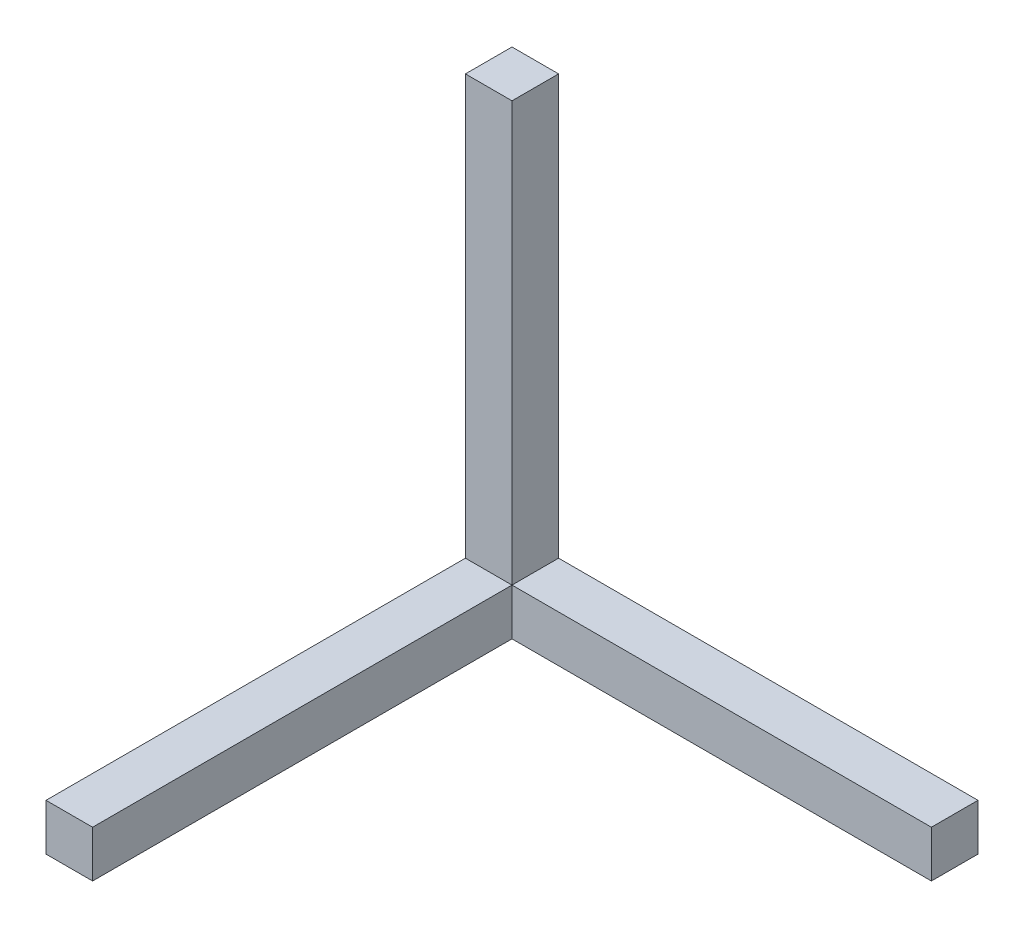
SolidWorks part; units mm, degrees
ref_plane "Plan de face" through (0, 0, 0) normal (0, 0, 1) x (1, 0, 0)
ref_plane "Plan de dessus" through (0, 0, 0) normal (0, 1, 0) x (1, 0, 0)
ref_plane "Plan de droite" through (0, 0, 0) normal (1, 0, 0) x (0, 0, -1)
sketch "Sketch1" plane through (0, 0, 0) normal (0, 0, 1) x (1, 0, 0)
  line L0 (-102.7228, 57.2848) -> (-92.7228, 57.2848)
  line L2 (-102.7228, 57.2848) -> (-102.7228, -42.7152)
  line L3 (-102.7228, -42.7152) -> (-2.7228, -42.7152)
  line L7 (-2.7228, -32.7152) -> (-92.7228, -32.7152)
  line L8 (-92.7228, 57.2848) -> (-92.7228, -32.7152)
  line L9 (-92.7228, -32.7152) -> (-102.7228, -32.7152)
  line L10 (-92.7228, -32.7152) -> (-92.7228, -42.7152)
  line L11 (-92.7228, -42.7152) -> (-102.7228, -42.7152)
  line L12 (-102.7228, -32.7152) -> (-102.7228, -42.7152)
  line L13 (-2.7228, -42.7152) -> (-2.7228, -32.7152)
  dimension "D1" = 100
  dimension "D2" = 100
  dimension "D3" = 10
  dimension "D4" = 10
extrude "Boss-Extrude1" add sketch "Sketch1" along normal blind 10 contours L9 L8 L2 | L7 L10 L3 region at (-97.7228, 12.2848, 0) region at (-47.7228, -37.7152, 0)
extrude "Boss-Extrude2" add sketch "Sketch1<4>" along normal blind 100 contours L10 L9 L2 L3 region at (-97.7228, -37.7152, 0)
sketch "Sketch1<4>" plane through (0, 0, 0) normal (0, 0, 1) x (1, 0, 0) same geometry as "Sketch1"
